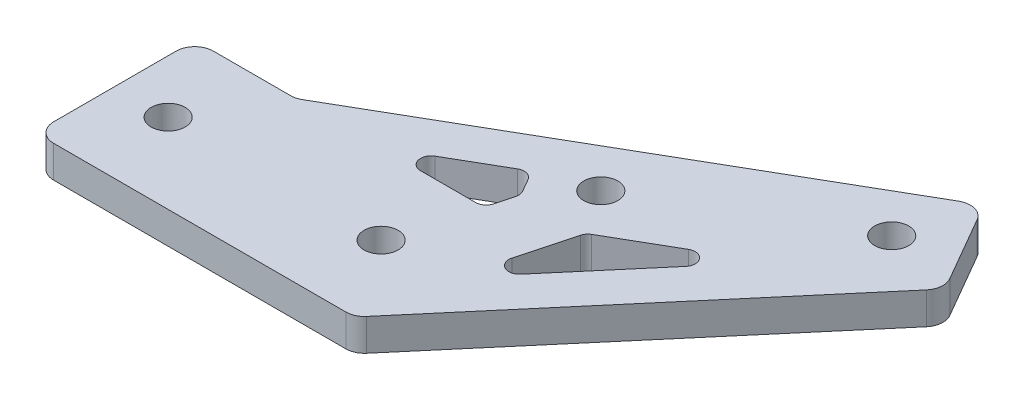
SolidWorks part; units mm, degrees
ref_plane "正面" through (0, 0, 0) normal (0, 0, 1) x (1, 0, 0)
ref_plane "平面" through (0, 0, 0) normal (0, 1, 0) x (1, 0, 0)
ref_plane "右側面" through (0, 0, 0) normal (1, 0, 0) x (0, 0, -1)
sketch "ｽｹｯﾁ1" plane through (0, 0, 0) normal (0, 1, 0) x (1, 0, 0)
  line L0 (164.476, -13.1178) -> (164.476, 1.8822) construction
  line L1 (164.476, 1.8822) -> (-55.524, 1.8822) construction
  line L3 (-55.524, -13.1178) -> (164.476, -13.1178) construction
  line L4 (26.6854, 10.5425) -> (31.6854, 1.8822) construction
  line L5 (31.6854, 1.8822) -> (334.7943, 176.8822) construction
  line L6 (334.7943, 176.8822) -> (329.7943, 185.5425) construction
  line L7 (329.7943, 185.5425) -> (26.6854, 10.5425) construction
  line L8 (164.476, -13.1178) -> (164.476, 1.8822) construction
  line L9 (164.476, 1.8822) -> (-55.524, 1.8822) construction
  line L11 (-55.524, -13.1178) -> (164.476, -13.1178) construction
  line L12 (26.6854, 10.5425) -> (31.6854, 1.8822) construction
  line L13 (31.6854, 1.8822) -> (334.7943, 176.8822) construction
  line L14 (334.7943, 176.8822) -> (329.7943, 185.5425) construction
  line L15 (329.7943, 185.5425) -> (26.6854, 10.5425) construction
  line L16 (29.47, 0) -> (419.1814, 225) construction
  line L17 (0, 0) -> (220, 0) construction
  line L18 (0, 0) -> (0, -15) construction
  line L19 (0, -15) -> (220, -15) construction
  line L20 (220, 0) -> (220, -15) construction
  line L21 (419.1814, 225) -> (414.1814, 233.6603) construction
  line L22 (414.1814, 233.6603) -> (24.47, 8.6603) construction
  line L23 (24.47, 8.6603) -> (29.47, 0) construction
  dimension "D1" = 15
  dimension "D2" = 220
  dimension "D3" = 29.47
  dimension "D4" = 30
  dimension "D5" = 450
  dimension "D6" = 10
sketch "ｽｹｯﾁ2" plane through (0, 0, 0) normal (0, 1, 0) x (1, 0, 0)
  line L0 (29.47, 0) -> (419.1814, 225) construction
  line L1 (24.47, 8.6603) -> (29.47, 0) construction
  line L2 (414.1814, 233.6603) -> (24.47, 8.6603) construction
  line L3 (220, 0) -> (220, -15) construction
  line L4 (0, -15) -> (220, -15) construction
  line L6 (0, 0) -> (220, 0) construction
  line L7 (29.47, 0) -> (419.1814, 225) construction
  line L8 (24.47, 8.6603) -> (29.47, 0) construction
  line L9 (414.1814, 233.6603) -> (24.47, 8.6603) construction
  line L10 (220, 0) -> (220, -15) construction
  line L11 (0, -15) -> (220, -15) construction
  line L13 (0, 0) -> (220, 0) construction
  line L14 (26.97, 4.3301) -> (48.6206, 16.8301) construction
  line L15 (0, -7.5) -> (25, -7.5) construction
  line L16 (24.47, 8.6603) -> (9.47, 0)
  line L18 (24.47, 8.6603) -> (50.4508, 23.6603)
  line L19 (50.4508, 23.6603) -> (55.4508, 15)
  line L20 (55.4508, 15) -> (30, -15)
  line L21 (30, -15) -> (0, -15)
  line L22 (0, -15) -> (0, 0)
  line L23 (0, 0) -> (9.47, 0)
  circle A0 centre (48.6206, 16.8301) radius 1.6
  circle A1 centre (25, -7.5) radius 1.6
  circle A2 centre (31.3001, 6.8301) radius 1.6
  circle A3 centre (5, -7.5) radius 1.6
  point P24 (0, -7.5)
  dimension "D3" = 3.2
  dimension "D4" = 3.2
  dimension "D5" = 3.2
  dimension "D6" = 3.2
  dimension "D1" = 25
  dimension "D2" = 25
  dimension "D7" = 5
  dimension "D8" = 5
  dimension "D9" = 5
  dimension "D10" = 5
extrude "ﾎﾞｽ - 押し出し1" add sketch "ｽｹｯﾁ2" along normal mid plane 3
sketch "ｽｹｯﾁ3" plane through (0, 1.5, 0) normal (0, 1, 0) x (1, 0, 0)
  line L0 (0, -15) -> (220, -15) construction
  line L1 (0, 0) -> (220, 0) construction
  line L2 (414.1814, 233.6603) -> (24.47, 8.6603) construction
  line L3 (24.47, 8.6603) -> (29.47, 0) construction
  line L4 (29.47, 0) -> (419.1814, 225) construction
  line L5 (0, -15) -> (220, -15)
  line L6 (0, 0) -> (220, 0)
  line L7 (414.1814, 233.6603) -> (24.47, 8.6603)
  line L8 (24.47, 8.6603) -> (29.47, 0)
  line L9 (29.47, 0) -> (419.1814, 225)
  line L10 (48.9867, 18.1962) -> (12.3252, -2.9704)
  line L11 (12.3252, -2.9704) -> (7.2558, -11)
  line L12 (7.2558, -11) -> (28.1479, -11)
  line L13 (28.1479, -11) -> (50.5782, 15.4396)
  line L14 (50.5782, 15.4396) -> (48.9867, 18.1962)
  line L15 (50.4508, 23.6603) -> (9.47, 0)
  line L16 (9.47, 0) -> (0, 0)
  line L17 (0, -15) -> (30, -15)
  line L18 (30, -15) -> (55.4508, 15)
  line L19 (55.4508, 15) -> (50.4508, 23.6603)
  line L20 (50.4508, 23.6603) -> (9.47, 0)
  line L22 (0, -15) -> (30, -15)
  line L23 (30, -15) -> (55.4508, 15)
  line L24 (55.4508, 15) -> (50.4508, 23.6603)
  line L25 (27.879, 2.7557) -> (27.1406, 0)
  line L26 (34.0628, 2.6517) -> (33.3523, 0)
  line L27 (0, -10.2338) -> (25, -7.5) construction
  line L28 (52.9508, 19.3301) -> (31.3001, 6.8301) construction
  line L29 (15.8097, 3.6603) -> (40.2703, -2.8939) construction
  line L30 (34.0628, 2.6517) -> (31.4468, -7.1115)
  line L37 (9.47, 0) -> (0, -15) construction
  line L38 (9.47, 0) -> (0, 0)
  line L39 (0, 0) -> (0, -15)
  line L40 (0, 0) -> (0, -15)
  dimension "D3" = 15
  dimension "D4" = 6
  dimension "D5" = 3.75
  dimension "D1" = 0
  dimension "D2" = 4
extrude "ｶｯﾄ - 押し出し1" cut sketch "ｽｹｯﾁ3" against normal blind 3 contours L25 L8 L10 L6 | L9 L26 L6 L13 | L6 L30 L13 region at (34.093, 1.5, 2.3705) region at (38.2121, 1.5, -3.3745) region at (24.0462, 1.5, -1.8254)
fillet "ﾌｨﾚｯﾄ1" radius 1 7 edges at (45.1695, 0, -9.0641) (17.47, 0, 0) (26.47, 0, -5.1962) (27.879, 0, -2.7557) (27.1406, 0, 0) (31.4468, 0, 7.1115) (34.0628, 0, -2.6517)
fillet "ﾌｨﾚｯﾄ2" radius 1.75 6 edges at (50.4508, 0, -23.6603) (55.4508, 0, -15) (30, 0, 15) (9.47, 0, 0) (0, 0, 0) (0, 0, 15)
sketch "ｽｹｯﾁ4" plane through (0, -1.5, 0) normal (0, -1, 0) x (1, 0, 0)
  line L0 (50.4508, -23.6603) -> (55.4508, -15) construction
  line L1 (24.47, -8.6603) -> (50.4508, -23.6603) construction
  line L2 (24.47, -8.6603) -> (29.47, 0) construction
  line L3 (29.47, 0) -> (419.1814, -225) construction
  line L4 (55.4508, -15) -> (30, 15) construction
  line L5 (0, 0) -> (220, 0) construction
  line L6 (30, 15) -> (0, 15) construction
  line L7 (0, 15) -> (0, 0) construction
  line L8 (50.4508, -23.6603) -> (55.4508, -15)
  line L9 (24.47, -8.6603) -> (50.4508, -23.6603)
  line L10 (24.47, -8.6603) -> (29.47, 0)
  line L11 (29.47, 0) -> (419.1814, -225)
  line L12 (55.4508, -15) -> (30, 15)
  line L13 (0, 0) -> (220, 0)
  line L14 (30, 15) -> (0, 15)
  line L15 (0, 15) -> (0, 0)
  circle A0 centre (29.47, 0) radius 1
  dimension "D1" = 2
